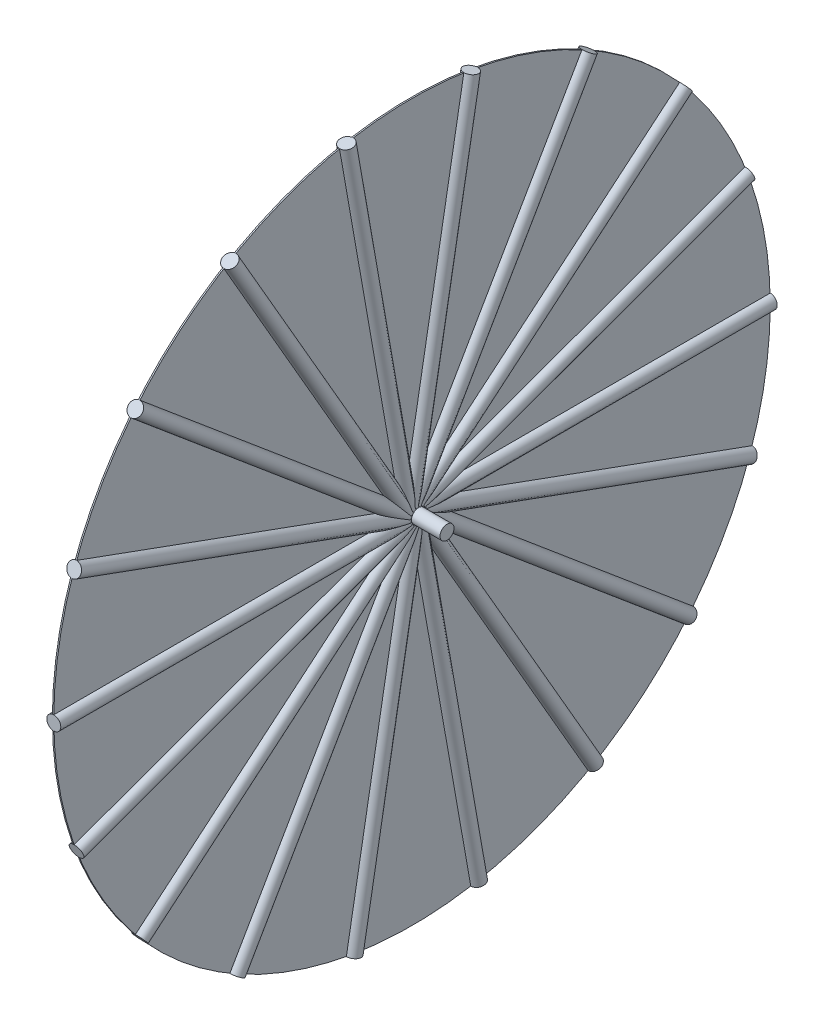
SolidWorks part; units mm, degrees
material "2024 Alloy"
ref_plane "Front Plane" through (0, 0, 0) normal (0, 0, 1) x (1, 0, 0)
ref_plane "Top Plane" through (0, 0, 0) normal (0, 1, 0) x (1, 0, 0)
ref_plane "Right Plane" through (0, 0, 0) normal (1, 0, 0) x (0, 0, -1)
sketch "Sketch3" plane through (39.7843, 0, 0) normal (0, 0, 1) x (1, 0, 0)
  line L1 (0, 0) -> (127.0469, 0)
  line L2 (0, 0) -> (0, 25.4)
  line L3 (0, 25.4) -> (127.0469, 25.4)
  line L4 (127.0469, 0) -> (127.0469, 25.4)
  point P4 (441.7381, 10.8627)
  point P5 (0, 0)
  point P6 (0, 0)
revolve "Revolve2" add sketch "Sketch3" angle 360 about L1
sketch "Sketch6" plane through (39.7843, 0, 0) normal (-1, 0, 0) x (0, 0, 1)
  line L1 (25.4, -12.7) -> (1300, -12.7)
  line L2 (25.4, -12.7) -> (25.4, 12.7)
  line L3 (25.4, 12.7) -> (1300, 12.7)
  line L4 (1300, -12.7) -> (1300, 12.7)
  point P5 (0, 0)
revolve "Revolve3" add sketch "Sketch6" angle 360 about L1
sketch "Sketch7" plane through (39.7843, 0, 0) normal (-1, 0, 0) x (0, 0, 1)
  circle A0 centre (0, 0) radius 1300
extrude "Boss-Extrude2" add sketch "Sketch7" along normal blind 5.08
pattern_circular "CirPattern1" count 18 over 360 about axis through (34.7043, 0, 0) along (-1, 0, 0) of "Revolve3"
